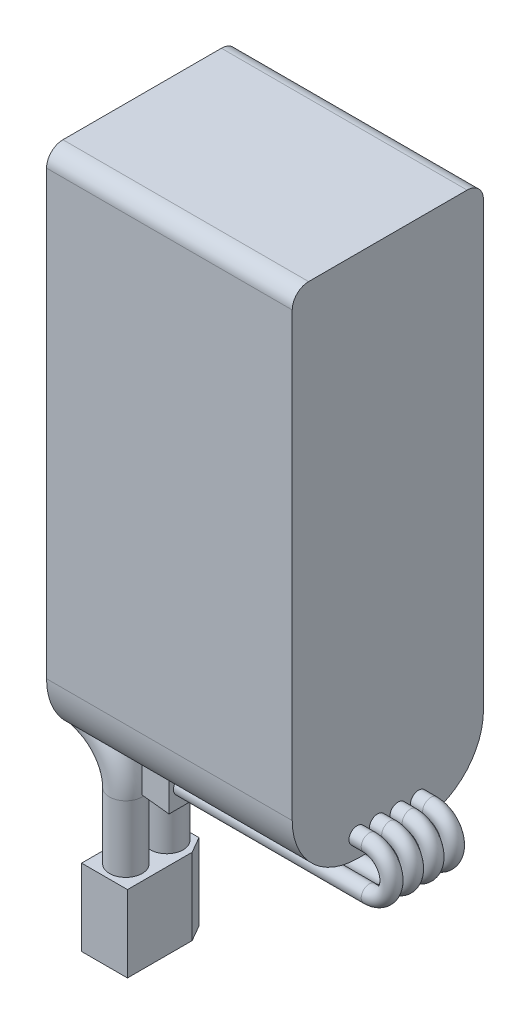
SolidWorks part; units mm, degrees
ref_plane "Front Plane" through (0, 0, 0) normal (1, 0, 0) x (0, 1, 0)
ref_plane "Top Plane" through (0, 0, 0) normal (0, 0, 1) x (0, 1, 0)
ref_plane "Right Plane" through (0, 0, 0) normal (0, 1, 0) x (-1, 0, 0)
sketch "Sketch1" plane through (0, 0, 0) normal (0, 0, 1) x (0, 1, 0)
  line L1 (-32, -15) -> (32, -15)
  line L2 (-32, -15) -> (-32, 15)
  line L3 (-32, 15) -> (32, 15)
  line L4 (32, -15) -> (32, 15)
  line L5 (-32, -15) -> (32, 15) construction
  line L6 (-32, 15) -> (32, -15) construction
  point P0 (0, 0)
  dimension "D1" = 64
  dimension "D2" = 30
extrude "Boss-Extrude1" add sketch "Sketch1" along normal blind 23.35
fillet "Fillet1" radius 2 2 edges at (0, 32, 0) (0, 32, 23.35)
sketch "Sketch2" plane through (-15, 0, 10) normal (1, 0, 0) x (0, 0, -1)
  line L0 (0.825, -29) -> (-4.175, -29) construction
  line L2 (-1.675, -29) -> (-1.675, -20.0823) construction
  line L3 (10, 30) -> (10, -32) construction
  line L4 (-13.35, 30) -> (-13.35, -32) construction
  line L5 (10, 30) -> (10, -32) construction
  line L6 (-13.35, 30) -> (-13.35, -32) construction
  line L7 (-13.35, -32) -> (10, -32) construction
  circle A0 centre (0.825, -29) radius 2
  circle A1 centre (-4.175, -29) radius 2
  dimension "D1" = 4
  dimension "D2" = 5
  dimension "D3" = 3
sketch "Sketch4" plane through (0, 0, 0) normal (0, 0, 1) x (0, 1, 0)
  line L0 (-29, 15) -> (-29, 17.8115)
  line L1 (-39.8327, 14.4947) -> (-47.9299, 14.4947)
  arc A0 (-29, 17.8115) -> (-33.9722, 18.6551) centre (-31.5576, 17.8115) ccw
  arc A1 (-33.9722, 18.6551) -> (-39.8327, 14.4947) centre (-39.8327, 20.7027) cw
sweep "Sweep2" add profiles "Sketch2" path "Sketch4"
sketch "Sketch5" plane through (15, 0, 0) normal (1, 0, 0) x (0, 1, 0)
  line L0 (-29.5, 12.925) -> (-29.5, 10.425) construction
  line L1 (-32, 0) -> (30, 0) construction
  line L2 (-32, 23.35) -> (30, 23.35) construction
  line L3 (-32, 0) -> (30, 0) construction
  line L4 (-32, 23.35) -> (30, 23.35) construction
  line L5 (-29.5, 11.675) -> (-24.2481, 11.675) construction
  line L6 (-32, 23.35) -> (-32, 0) construction
  circle A0 centre (-29.5, 12.925) radius 1
  circle A1 centre (-29.5, 10.425) radius 1
  circle A2 centre (-29.5, 15.425) radius 1
  circle A3 centre (-29.5, 7.925) radius 1
  point P14 (-29.8469, 8.5355)
  dimension "D1" = 2
  dimension "D2" = 2.5
  dimension "D3" = 2.5
  dimension "D4" = 2.5
  dimension "D5" = 2.5
sketch "Sketch6" plane through (0, 0, 0) normal (0, 0, 1) x (0, 1, 0)
  line L0 (-29.5, -16.4977) -> (-29.5, -15)
  line L1 (-34.9001, -16.4977) -> (-34.9001, 6.4232)
  arc A0 (-29.5, -16.4977) -> (-34.9001, -16.4977) centre (-32.2, -16.4977) cw
sweep "Sweep3" add profiles "Sketch5" path "Sketch6"
sketch "Sketch7" plane through (-6.4232, 0, 0) normal (-1, 0, 0) x (0, -1, 0)
  line L0 (34.9001, 11.675) -> (35.3785, 11.675) construction
  line L1 (32.6001, 6.375) -> (37.2001, 6.375)
  line L2 (32.6001, 6.375) -> (32.6001, 16.975)
  line L3 (32.6001, 16.975) -> (37.2001, 16.975)
  line L4 (37.2001, 6.375) -> (37.2001, 16.975)
  line L5 (32.6001, 6.375) -> (37.2001, 16.975) construction
  line L6 (32.6001, 16.975) -> (37.2001, 6.375) construction
  circle A0 centre (34.9001, 10.425) radius 1 construction
  circle A1 centre (34.9001, 12.925) radius 1 construction
  circle A2 centre (34.9001, 10.425) radius 1 construction
  circle A3 centre (34.9001, 12.925) radius 1 construction
  point P0 (34.9001, 11.675)
  dimension "D1" = 10.6
  dimension "D2" = 4.6
extrude "Boss-Extrude2" add sketch "Sketch7" along normal blind 3.5 draft 3
sketch "Sketch8" plane through (0, -47.9299, 0) normal (0, -1, 0) x (1, 0, 0)
  line L5 (-14.4947, 11.675) -> (-12.7903, 11.675) construction
  line L6 (-16.3531, 6.9116) -> (-12.8281, 6.9116)
  line L8 (-17.2947, 8.5426) -> (-17.2947, 16.775)
  line L9 (-17.2947, 16.775) -> (-11.6947, 16.775)
  line L10 (-11.6947, 8.8746) -> (-11.6947, 16.775)
  line L11 (-17.2947, 6.575) -> (-11.6947, 16.775) construction
  line L12 (-17.2947, 16.775) -> (-11.8318, 6.8247) construction
  line L13 (-16.3531, 6.9116) -> (-17.2947, 8.5426)
  line L14 (-12.8281, 6.9116) -> (-11.6947, 8.8746)
  circle A4 centre (-14.4947, 14.175) radius 2 construction
  circle A5 centre (-14.4947, 9.175) radius 2 construction
  circle A6 centre (-14.4947, 14.175) radius 2 construction
  circle A7 centre (-14.4947, 9.175) radius 2 construction
  point P6 (-14.4947, 11.675)
  dimension "D1" = 10.2
  dimension "D2" = 5.6
  dimension "D3" = 60
  dimension "D4" = 60
  dimension "D5" = 1
  dimension "D6" = 1
extrude "Boss-Extrude3" add sketch "Sketch8" along normal blind 9.35
fillet "Fillet3" radius 8 2 edges at (0, -32, 0) (0, -32, 23.35)
